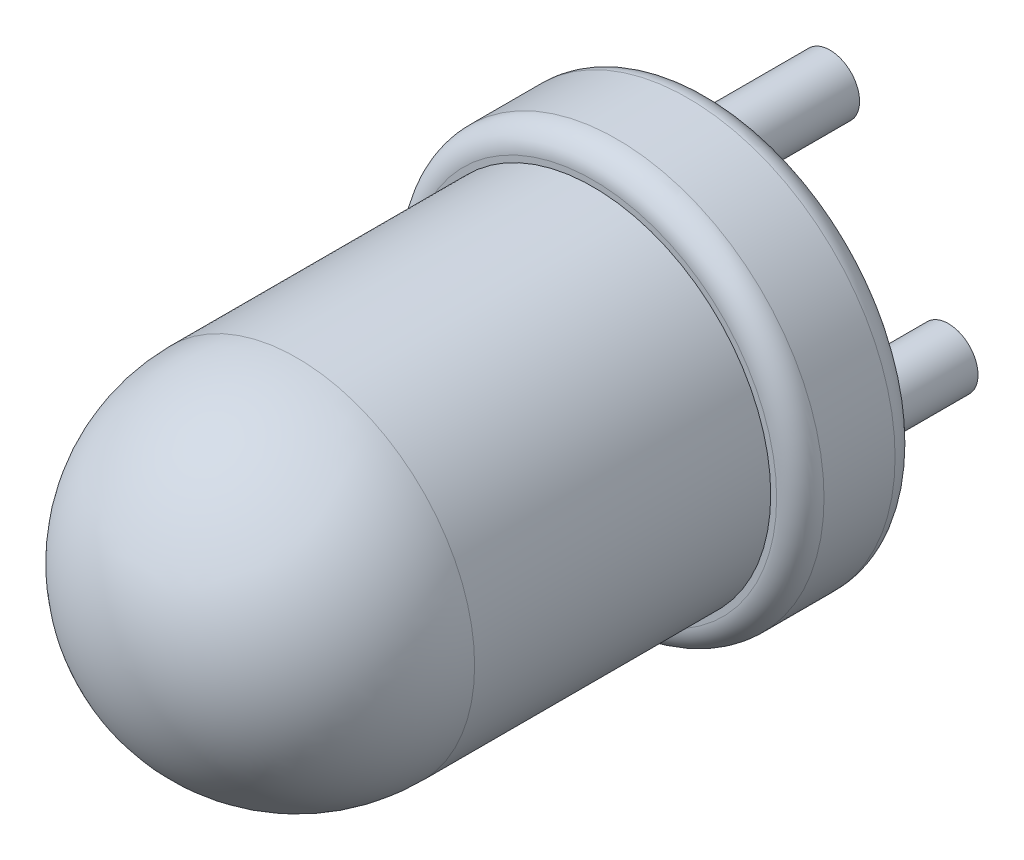
SolidWorks part; units mm, degrees
ref_plane "前视基准面" through (0, 0, 0) normal (0, 0, 1) x (1, 0, 0)
ref_plane "上视基准面" through (0, 0, 0) normal (0, 1, 0) x (1, 0, 0)
ref_plane "右视基准面" through (0, 0, 0) normal (1, 0, 0) x (0, 0, -1)
other "Configuration Table"
sketch "草图1" plane through (0, 0, 0) normal (0, 0, 1) x (1, 0, 0)
  line L0 (0, 1.25) -> (0, -1.25)
  circle A0 centre (0, 0) radius 1.75
  circle A1 centre (0, 0) radius 1.5
  circle A2 centre (0, 1.25) radius 0.25
  circle A3 centre (0, -1.25) radius 0.25
  point P4 (0, 0)
  dimension "D1" = 3
  dimension "D2" = 3.5
  dimension "D3" = 0.5
  dimension "D4" = 2.5
extrude "凸台-拉伸1" add sketch "草图1" along normal blind 5 contours A1
extrude "凸台-拉伸2" add sketch "草图1<6>" along normal blind 1 contours A0
sketch "草图1<6>" plane through (0, 0, 0) normal (0, 0, 1) x (1, 0, 0) same geometry as "草图1"
extrude "凸台-拉伸3" add sketch "草图1<7>" against normal blind 1 contours A2
sketch "草图1<7>" plane through (0, 0, 0) normal (0, 0, 1) x (1, 0, 0) same geometry as "草图1"
extrude "凸台-拉伸4" add sketch "草图1<9>" against normal blind 2 contours A3
sketch "草图1<9>" plane through (0, 0, 0) normal (0, 0, 1) x (1, 0, 0) same geometry as "草图1"
fillet "圆角1" radius 1.5 1 edges at (1.5, 0, 5)
fillet "圆角2" radius 0.2 2 edges at (1.75, 0, 0) (1.75, 0, 1)
